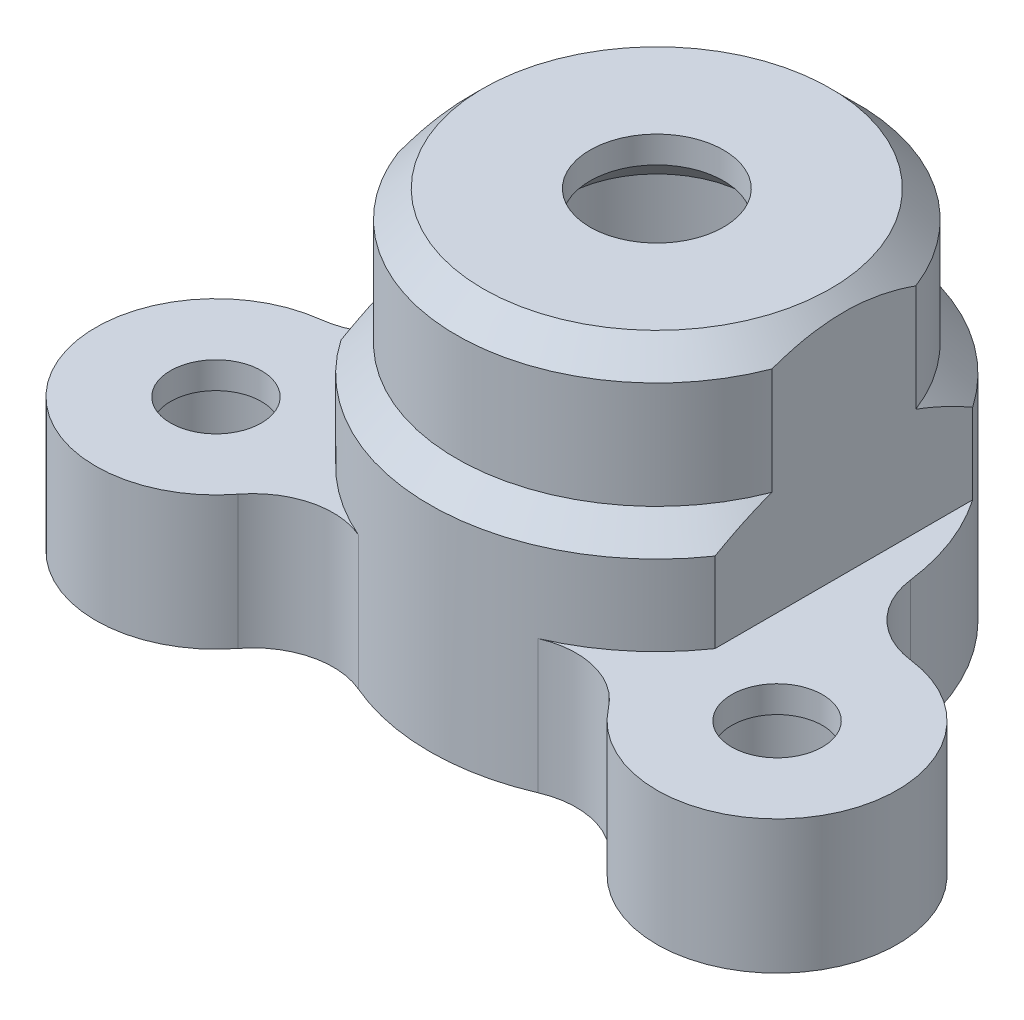
SolidWorks part; units mm, degrees
ref_plane "Plan de face" through (0, 0, 0) normal (0, 0, 1) x (1, 0, 0)
ref_plane "Plan de dessus" through (0, 0, 0) normal (0, 1, 0) x (1, 0, 0)
ref_plane "Plan de droite" through (0, 0, 0) normal (1, 0, 0) x (0, 0, -1)
sketch "Esquisse1" plane through (0, 0, 0) normal (0, 1, 0) x (1, 0, 0)
  line L0 (0, 8.5) -> (0, -8.5) construction
  line L1 (0, 0) -> (-7.3612, 4.25) construction
  line L2 (0, 0) -> (7.3612, 4.25) construction
  line L3 (-10.5, -1.5) -> (-6.3246, -1.5)
  line L4 (10.5, -1.5) -> (6.3246, -1.5)
  circle A0 centre (0, 0) radius 5.5 construction
  circle A2 centre (-10.5, -6) radius 1.7 construction
  arc A3 (-6, -6.0207) -> (6, -6.0207) centre (0, 0) ccw
  circle A4 centre (-10.5, -6) radius 2.5
  arc A5 (-10.5, -1.5) -> (-6, -6.0207) centre (-10.5, -6) ccw
  circle A6 centre (0, 0) radius 6.5
  circle A8 centre (10.5, -6) radius 1.7 construction
  circle A10 centre (10.5, -6) radius 2.5
  arc A11 (10.5, -1.5) -> (6, -6.0207) centre (10.5, -6) cw
  arc A12 (8.3666, -1.5) -> (-8.3666, -1.5) centre (0, 0) ccw construction
  point P4 (8.4123, -1.5)
  point P13 (8.4123, -1.5)
  point P15 (8.4123, -1.5)
  point P16 (0, 0)
  point P21 (0, 0)
  dimension "D1" = 11
  dimension "D4" = 3.4
  dimension "D5" = 2
  dimension "D6" = 3
  dimension "D7" = 5
  dimension "D9" = 1
  dimension "D2" = 10.5
  dimension "D3" = 6
  dimension "D10" = 60
  dimension "D11" = 60
sketch "Esquisse2" plane through (0, 0, 0) normal (0, 0, 1) x (1, 0, 0)
  line L0 (0, 9) -> (0, 0) construction
  line L1 (-2.5, 9) -> (-2.5, 8)
  line L2 (-2.5, 8) -> (-3.5, 7)
  line L3 (-3.5, 7) -> (-5.5, 7)
  line L4 (-5.5, 7) -> (-5.5, 3)
  line L5 (-5.5, 3) -> (-6.5, 2)
  line L7 (-8.5, 0) -> (-8.5, 3)
  line L8 (-8.5, 9) -> (-7.5, 9) construction
  line L9 (-6.5, 2) -> (-6.5, 0)
  line L10 (-8.5, 3) -> (-7.5, 4)
  line L11 (-6.5, 0) -> (-8.5, 0)
  line L12 (-7.5, 4) -> (-7.5, 8)
  line L13 (-8.5, 3) -> (-8.5, 9) construction
  line L14 (-6.5, 9) -> (-2.5, 9)
  line L15 (-7.5, 8) -> (-6.5, 9)
  point P13 (0, 0)
  dimension "D1" = 2.5
  dimension "D2" = 5.5
  dimension "D3" = 2
  dimension "D4" = 1
  dimension "D5" = 1
  dimension "D6" = 4
  dimension "D7" = 1
  dimension "D8" = 8.5
  dimension "D9" = 2
  dimension "D10" = 1
  dimension "D11" = 1
revolve "Révolution1" add sketch "Esquisse2" angle 360 about L0
extrude "Boss.-Extru.1" add sketch "Esquisse1" against normal blind 5 contours A11 A6 A5 A3 A4 A10 | A4 | A10 region at (-8.4123, 0, 1.8132) region at (-10.5, 0, 6) region at (10.5, 0, 6)
extrude "Enlèv. mat.-Extru.3" cut sketch "Esquisse1<7>" along normal blind 4 from surface contours A4 | A10 region at (-10.5, 0, 6) region at (10.5, 0, 6) starting at face at (0, -5, 6.0582)
sketch "Esquisse1<7>" plane through (0, 0, 0) normal (0, 1, 0) x (1, 0, 0) same geometry as "Esquisse1"
sketch "Esquisse9" plane through (0, -5, 0) normal (0, -1, 0) x (-1, 0, 0)
  point P0 (-10.5, -6)
  point P3 (10.5, -6)
hole_wizard "M3 Clearance Hole2" positions "Esquisse9" profile "Esquisse8" hole size "M3" standard "ANSI Metric" end condition up to next
sketch "Esquisse8" plane through (10.5, -5, 6) normal (1, 0, 0) x (0, 0, -1)
  line L0 (0, 0) -> (0, 5)
  line L1 (0, 5) -> (1.7, 5)
  line L2 (1.7, 5) -> (1.7, 0)
  line L5 (1.7, 0) -> (0, 0)
  line L11 (0, -6.35) -> (0, 107.95) construction
  dimension "Thru Hole Dia." = 3.4
  dimension "Thru Hole Depth" = 5
sketch "Esquisse10" plane through (0, -5, 0) normal (0, -1, 0) x (1, 0, 0)
  line L3 (10.5, 1.5) -> (6.3246, 1.5) construction
  line L4 (8.3666, 1.5) -> (6.3246, 1.5) construction
  line L5 (6.3246, 1.5) -> (8.3666, 1.5)
  line L6 (-6.3246, 1.5) -> (-8.3666, 1.5)
  arc A1 (-8.3666, 1.5) -> (8.3666, 1.5) centre (0, 0) ccw
  arc A2 (-6.3246, 1.5) -> (6.3246, 1.5) centre (0, 0) ccw
  point P32 (5.5589, -4.9901)
  line M19 (-10.5, 1.5) -> (-6.3246, 1.5)
  line M21 (6.3246, 1.5) -> (10.5, 1.5)
extrude "Boss.-Extru.3" add sketch "Esquisse10" along normal blind 5 from surface contours A2 A1 M19 | A2 A1 | A2 A1 M21 region at (7.3456, -5, 1.3028) starting at face at (0, 0, -3)
sketch "Esquisse11" plane through (0, 9, 0) normal (0, 1, 0) x (1, 0, 0)
  line L0 (-7, 4.8218) -> (-7, -4.8218)
  line L1 (7, 4.8218) -> (7, -4.8218)
  circle A0 centre (0, 0) radius 8.5 construction
  arc A1 (-8.3666, -1.5) -> (-6, -6.0207) centre (0, 0) ccw construction
  arc A2 (-7, -4.8218) -> (-7, 4.8218) centre (0, 0) cw
  arc A3 (7, 4.8218) -> (7, -4.8218) centre (0, 0) cw
  dimension "D1" = 14
extrude "Enlèv. mat.-Extru.5" cut sketch "Esquisse11" against normal up to surface (9 mm away) contours A2 L0 | A3 L1 region at (-7.6048, 9, 0) region at (7.6048, 9, 0) up to face at (-10.5, 0, 7.7)
fillet "Congé5" radius 3 4 edges at (-8.3666, -2.5, 1.5) (8.3666, -2.5, 1.5) (6, -2.5, 6.0207) (-6, -2.5, 6.0207)
chamfer "Chanfrein5" distance 0.5 angle 45 2 edges at (-10.5, -5, 8.5) (10.5, -5, 8.5)
